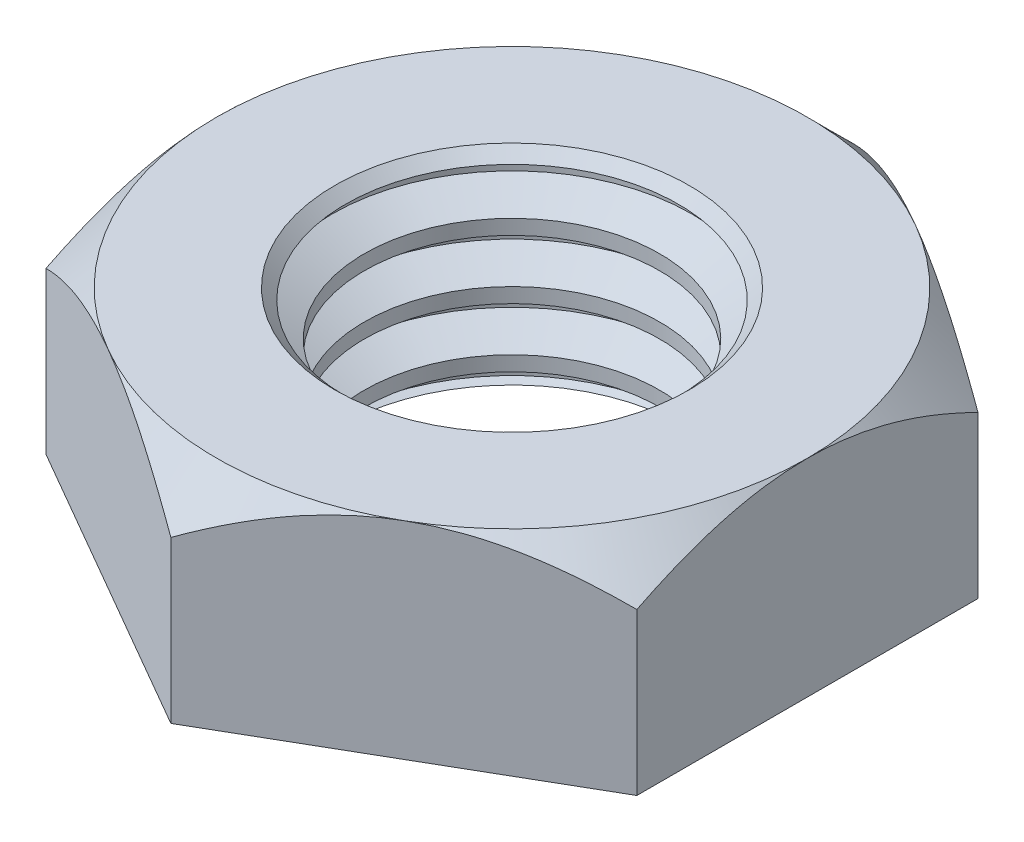
SolidWorks part; units mm, degrees
ref_plane "Front" through (0, 0, 0) normal (0, 0, 1) x (1, 0, 0)
ref_plane "Top" through (0, 0, 0) normal (0, 1, 0) x (1, 0, 0)
ref_plane "Right" through (0, 0, 0) normal (1, 0, 0) x (0, 0, -1)
sketch "Sketch1" plane through (0, 0, 0) normal (0, 1, 0) x (1, 0, 0)
  line L1 (0, 4.5827) -> (-3.9688, 2.2914)
  line L2 (-3.9688, 2.2914) -> (-3.9688, -2.2914)
  line L3 (-3.9688, -2.2914) -> (0, -4.5827)
  line L4 (0, -4.5827) -> (3.9688, -2.2914)
  line L5 (3.9688, -2.2914) -> (3.9688, 2.2914)
  line L6 (3.9688, 2.2914) -> (0, 4.5827)
  circle A0 centre (0, 0) radius 3.9688 construction
  dimension "Hex Flats" = 7.9375
extrude "Extrude1" add sketch "Sketch1" along normal blind 2.7781
sketch "Sketch3" plane through (0, 0, 0) normal (1, 0, 0) x (0, 0, -1)
  line L0 (3.9688, 2.7781) -> (4.5827, 2.1642)
  line L1 (2.2914, 2.7781) -> (4.5827, 2.7781) construction
  line L2 (4.5827, 2.7781) -> (4.5827, 0) construction
  line L3 (4.5827, 2.1642) -> (4.5827, 2.7781)
  line L4 (4.5827, 2.7781) -> (3.9688, 2.7781)
  line L5 (0, 0.542) -> (0, -0.542) construction
  dimension "D1" = 45
  dimension "D2" = 7.9375
revolve "Cut-Revolve2" cut sketch "Sketch3" angle 360 about L5
sketch "Sketch2" plane through (0, 0, 0) normal (0, 0, 1) x (1, 0, 0)
  line L0 (0, 1.6636) -> (0, -0.3796) construction
  line L1 (0, 2.7781) -> (1.9834, 2.7781)
  line L3 (0, 2.7781) -> (3.9688, 2.7781) construction
  line L4 (0, 1.9844) -> (1.9834, 1.9844)
  line L5 (1.9834, 2.7781) -> (2.413, 2.5301)
  line L6 (2.413, 2.5301) -> (2.413, 2.4309)
  line L7 (2.413, 2.4309) -> (1.9834, 2.1828)
  line L9 (1.9834, 1.9844) -> (1.9834, 2.1828)
  line L10 (0, 1.9844) -> (0, 2.7781)
  line L11 (1.9834, 2.7781) -> (1.9834, 2.1828) construction
  line L12 (2.413, 2.4805) -> (1.9834, 2.4805) construction
  dimension "D1" = 60
  dimension "D2" = 0.1984
  dimension "D5" = 0.0992
  dimension "Pitch" = 0.7937
  dimension "Major Dia." = 4.826
revolve "Cut-Revolve1" cut sketch "Sketch2" angle 360 about L0
pattern_linear "LPattern2" count 4 spacing 0.7937 along (0, -1, 0) of "Cut-Revolve1"
chamfer "Chamfer1" distance 0.3969 angle 45 1 edges at (0, 2.7781, 1.9834) first distance on face at (0, 2.7781, 0)
equation "\"D5@Sketch2\"=\"Pitch@Sketch2\"/8"
equation "\"D2@Sketch2\"=\"Pitch@Sketch2\"/4"
equation "\"D3@LPattern2\"=\"Pitch@Sketch2\""
equation "\"D1@LPattern2\"=\"Height@Extrude1\"/\"Pitch@Sketch2\""
equation "\"D2@Sketch3\"=\"Hex Flats@Sketch1\""
equation "\"D1@Chamfer1\"=\"Pitch@Sketch2\"/2"
